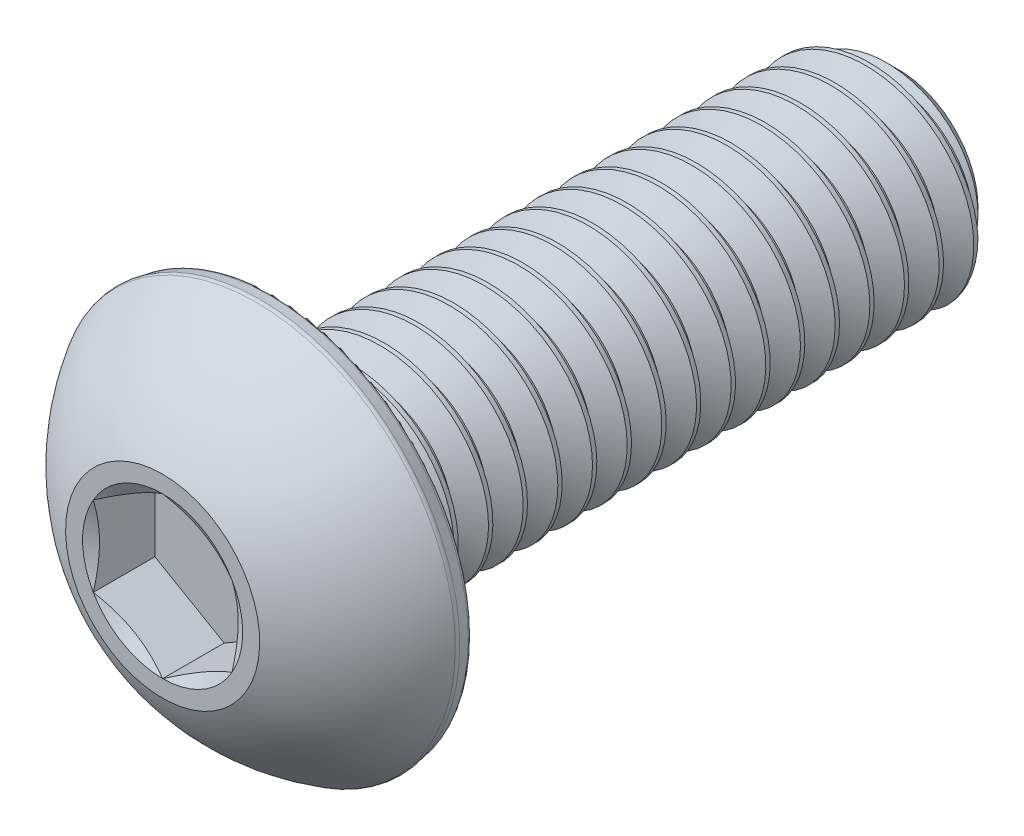
SolidWorks part; units mm, degrees
ref_plane "Front Plane" through (0, 0, 0) normal (0, 0, 1) x (1, 0, 0)
ref_plane "Top Plane" through (0, 0, 0) normal (0, 1, 0) x (1, 0, 0)
ref_plane "Right Plane" through (0, 0, 0) normal (1, 0, 0) x (0, 0, -1)
sketch "Sketch1" plane through (0, 0, 0) normal (1, 0, 0) x (0, 0, -1)
  line L0 (-8.4265, 0) -> (8.4265, 0) construction
  line L1 (-8.4265, 0) -> (-8.4265, 4.5847)
  line L2 (-8.4265, 4.5847) -> (-5.8611, 4.5847)
  line L3 (-5.8611, 4.5847) -> (-5.8611, 2.413)
  line L4 (-5.8611, 2.413) -> (8.4264, 2.413)
  line L5 (8.4264, 2.413) -> (8.4265, 0)
  point P2 (0, 0)
  point P4 (7.6327, 0)
  point P9 (7.2358, 2.413)
  point P10 (7.2358, -2.413)
  point P11 (8.4264, -2.413)
  point P15 (-7.0155, 0)
  dimension "Head Height" = 2.5654
  dimension "Head Diameter" = 9.1694
  dimension "Length" = 14.2875
  dimension "Screw Size Decimal Equivalent" = 4.826
  dimension "Thread Pitch" = 0.7937
  dimension "D1" = 1.1906
  dimension "D2" = 1.411
sketch "Sketch2" plane through (0, 0, 0) normal (0, 0, 1) x (1, 0, 0)
  line L0 (0, 2.413) -> (0, 0) construction
  line L1 (0, 1.8331) -> (-1.5875, 0.9165)
  line L2 (-1.5875, 0.9165) -> (-1.5875, -0.9165)
  line L3 (-1.5875, -0.9165) -> (0, -1.8331)
  line L4 (0, -1.8331) -> (1.5875, -0.9165)
  line L5 (1.5875, -0.9165) -> (1.5875, 0.9165)
  line L6 (1.5875, 0.9165) -> (0, 1.8331)
  circle A0 centre (0, 0) radius 1.5875 construction
  circle A1 centre (0, 0) radius 2.2225
  point P10 (0, 2.2225)
  dimension "D1" = 4.445
  dimension "Drive Size" = 3.175
sketch "Sketch3" plane through (0, 0, 0) normal (1, 0, 0) x (0, 0, -1)
  line L0 (-8.4265, 0) -> (-8.4265, 2.2225)
  line L1 (-8.4265, 0) -> (-8.4265, 4.5847) construction
  line L2 (-8.4265, 4.5847) -> (-5.8611, 4.5847) construction
  line L3 (-6.2459, 4.5847) -> (-5.8611, 4.5168)
  line L4 (-5.8611, 4.5847) -> (-5.8611, 2.413) construction
  line L5 (-5.8611, 4.5168) -> (-5.8611, 2.413)
  line L6 (-8.4265, 0) -> (8.4265, 0) construction
  line L7 (-8.4265, 0) -> (8.4265, 0)
  line L8 (8.4265, 0) -> (8.4264, 1.8177)
  line L9 (8.4264, 2.413) -> (8.4264, 0) construction
  line L10 (8.4264, 1.8177) -> (7.8311, 2.413)
  line L11 (-5.8611, 2.413) -> (8.4264, 2.413) construction
  line L12 (7.8311, 2.413) -> (-5.8611, 2.413)
  arc A0 (-8.4265, 2.2225) -> (-6.2459, 4.5847) centre (-3.6491, 0) cw
  dimension "D1" = 0.3848
  dimension "D2" = 10
  dimension "D3" = 45
  dimension "D4" = 0.5953
revolve "Revolve1" add sketch "Sketch3" angle 360 about L7
sketch "Sketch4" plane through (0, 0, 8.4265) normal (0, 0, 1) x (1, 0, 0)
  line L0 (-1.5875, -0.9165) -> (0, -1.8331) construction
  line L1 (-1.5875, 0.9165) -> (-1.5875, -0.9165) construction
  line L2 (0, 1.8331) -> (-1.5875, 0.9165) construction
  line L3 (1.5875, 0.9165) -> (0, 1.8331) construction
  line L4 (1.5875, -0.9165) -> (1.5875, 0.9165) construction
  line L5 (0, -1.8331) -> (1.5875, -0.9165) construction
  line L6 (-1.5875, -0.9165) -> (0, -1.8331)
  line L7 (-1.5875, 0.9165) -> (-1.5875, -0.9165)
  line L8 (0, 1.8331) -> (-1.5875, 0.9165)
  line L9 (1.5875, 0.9165) -> (0, 1.8331)
  line L10 (1.5875, -0.9165) -> (1.5875, 0.9165)
  line L11 (0, -1.8331) -> (1.5875, -0.9165)
extrude "Cut-Extrude1" cut sketch "Sketch4" against normal up to vertex (1.411 mm away) up to point (0, 0, 7.0155)
sketch "Sketch5" plane through (0, 0, 8.4265) normal (0, 0, 1) x (1, 0, 0)
  circle A0 centre (0, 0) radius 1.8331
extrude "Cut-Extrude2" cut sketch "Sketch5" against normal up to vertex (1.411 mm away) draft 60 up to point (0, 0, 7.0155)
fillet "Fillet1" radius 0.1283 2 edges at (4.5847, 0, 6.2459) (4.5168, 0, 5.8611)
split "Split1" bodies to split 106 resulting bodies 107 108 split by face at (4.4092, 0, 5.8611)
sketch "Sketch6" plane through (0, 0, -8.4265) normal (0, 0, -1) x (-1, 0, 0)
  circle A0 centre (0, 0) radius 2.413 construction
  circle A1 centre (0, 0) radius 2.413
curve "Helix/Spiral1" pitch 0.7937 height 15.0812 radius 2.413 centre (0, 0, -8.4265) axis (0, 0, 1) start towards (0, 1, 0)
sketch "Sketch7" plane through (0, 0, 0) normal (1, 0, 0) x (0, 0, -1)
  line L0 (8.3768, 2.4989) -> (8.7737, 1.8115) construction
  line L1 (8.7737, 1.8115) -> (9.1706, 2.4989) construction
  line L2 (9.1706, 2.4989) -> (8.3768, 2.4989) construction
  line L3 (8.4016, 2.456) -> (9.1458, 2.456)
  line L4 (9.1458, 2.456) -> (8.8233, 1.8974)
  line L5 (8.8233, 1.8974) -> (8.7241, 1.8974)
  line L6 (8.7241, 1.8974) -> (8.4016, 2.456)
  line L7 (8.7737, 1.8974) -> (8.7737, 1.8115) construction
  line L8 (8.4264, 2.413) -> (9.121, 2.413) construction
  line L9 (8.7737, 2.4989) -> (8.7737, 2.413) construction
  point P12 (8.7737, 2.456)
  dimension "D1" = 0.7937
  dimension "D2" = 0.0992
sweep "Cut-Sweep1" cut profiles "Sketch7" path "Helix/Spiral1" align with end faces yes
sketch "Sketch8" plane through (0, 0, 5.8611) normal (0, 0, -1) x (-1, 0, 0)
  circle A0 centre (0, 0) radius 2.4989
extrude "Boss-Extrude1" add sketch "Sketch8" along normal up to vertex (13.0969 mm away) draft 45 up to point (0, 2.413, -7.2358)
equation "\"D1@Sketch1\"=\"Thread Pitch@Sketch1\"*1.5"
equation "\"D2@Sketch1\"=0.55*\"Head Height@Sketch1\""
equation "\"D1@Sketch2\"=\"Drive Size@Sketch2\"*1.4"
equation "\"D1@Sketch3\"=0.15*\"Head Height@Sketch1\""
equation "\"D4@Sketch3\"=0.75*\"Thread Pitch@Sketch1\""
equation "\"D1@Fillet1\"=.05*\"Head Height@Sketch1\""
equation "\"D4@Helix/Spiral1\"=\"Thread Pitch@Sketch1\""
equation "\"D3@Helix/Spiral1\"=\"Length@Sketch1\"+\"Thread Pitch@Sketch1\""
equation "\"D2@Sketch7\"=\"D1@Sketch7\"/8"
equation "\"D1@Sketch7\"=\"Thread Pitch@Sketch1\""
